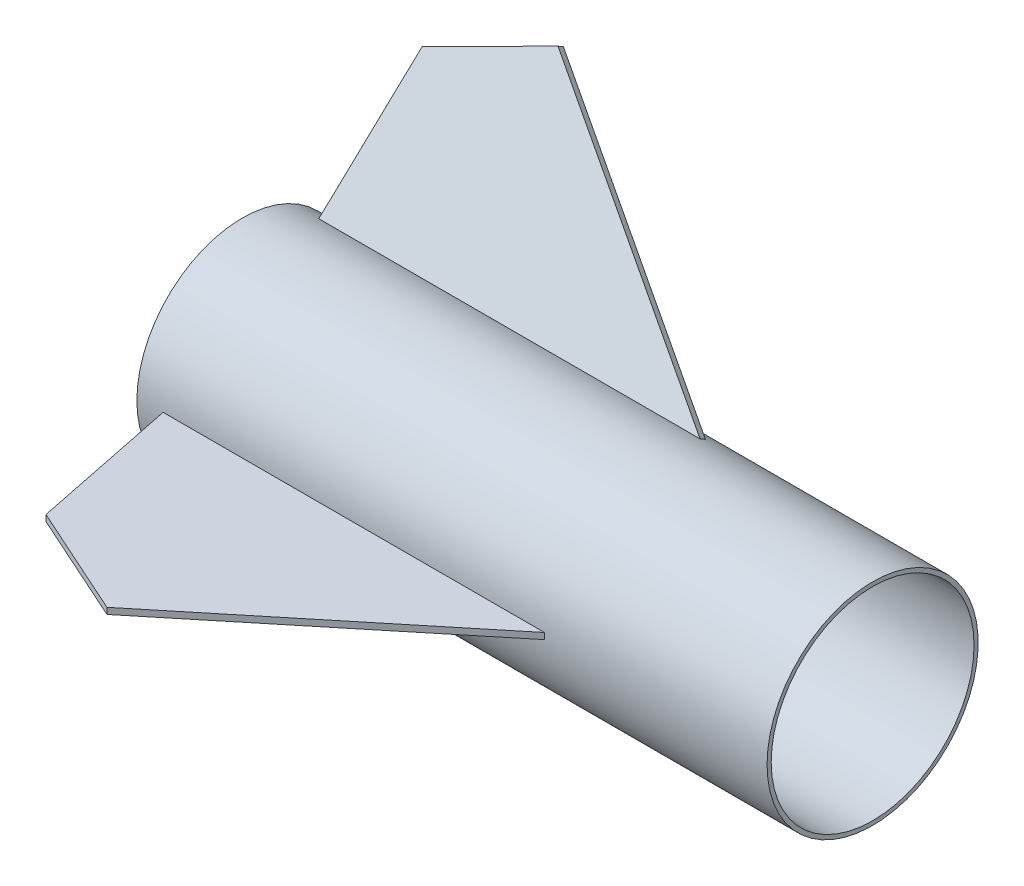
SolidWorks part; units mm, degrees
ref_plane "Front Plane" through (0, 0, 0) normal (1, 0, 0) x (0, 1, 0)
ref_plane "Top Plane" through (0, 0, 0) normal (0, 0, 1) x (0, 1, 0)
ref_plane "Right Plane" through (0, 0, 0) normal (0, 1, 0) x (-1, 0, 0)
sketch "Body Tube" plane through (0, 0, 0) normal (1, 0, 0) x (0, 1, 0)
  circle A2 centre (0, 0) radius 51.054
  circle A3 centre (0, 0) radius 49.0601
  point P4 (0, 0)
  dimension "D1" = 98.1202
  dimension "D2" = 102.108
  dimension "D3" = 1.9939
extrude "Boss-Extrude1" add sketch "Body Tube" along normal blind 304.8
sketch "Sketch2" plane through (0, 0, 0) normal (0, 1, 0) x (-1, 0, 0)
sketch "Sketch6" plane through (0, 0, 0) normal (0, 1, 0) x (-1, 0, 0)
  line L4 (-12.7, 51.054) -> (-197.104, 51.054)
  line L5 (0, 51.054) -> (-304.8, 51.054) construction
  line L6 (-197.104, 51.054) -> (-80.772, 146.304)
  line L9 (-80.772, 146.304) -> (-27.178, 122.174)
  line L10 (-27.178, 122.174) -> (-12.7, 51.054)
  dimension "D1" = 184.404
  dimension "D2" = 95.25
  dimension "D3" = 12.7
  dimension "D4" = 53.594
  dimension "D5" = 14.478
  dimension "D6" = 71.12
extrude "Boss-Extrude3" add sketch "Sketch6" along normal blind 1.5 and the other way blind 1.5 separate body
pattern_circular "CirPattern10" count 3 over 360 about axis through (304.8, 0, 0) along (-1, 0, 0) of bodies 103 101
